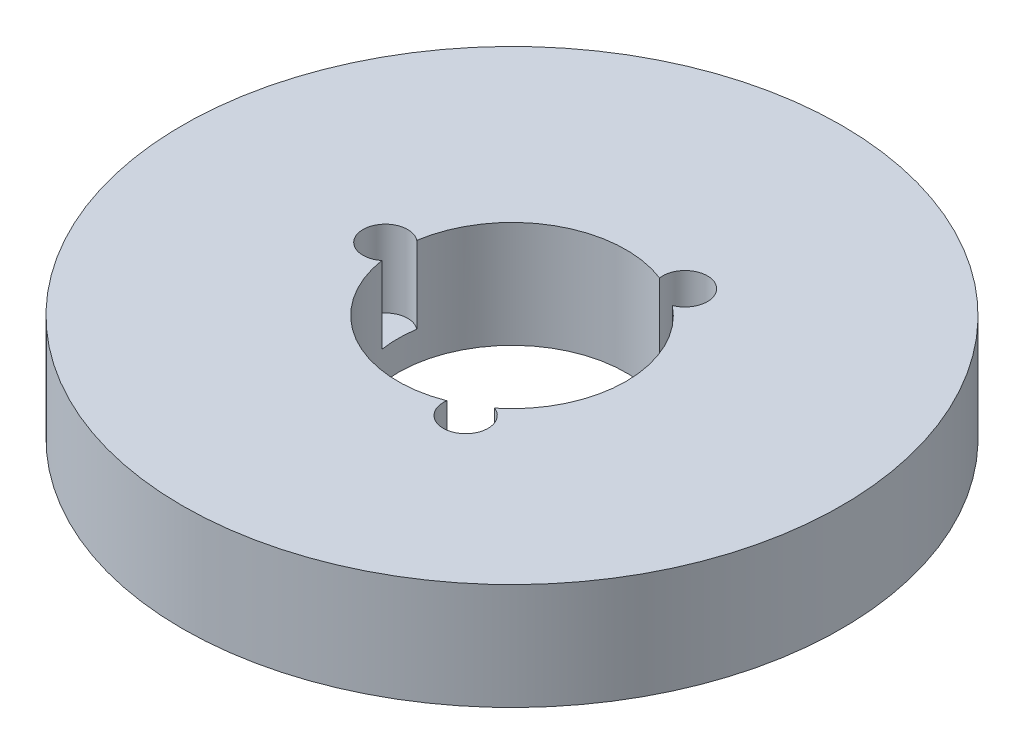
SolidWorks part; units mm, degrees
ref_plane "Front Plane" through (0, 0, 0) normal (0, 0, 1) x (1, 0, 0)
ref_plane "Top Plane" through (0, 0, 0) normal (0, 1, 0) x (1, 0, 0)
ref_plane "Right Plane" through (0, 0, 0) normal (1, 0, 0) x (0, 0, -1)
sketch "Sketch1" plane through (0, 0, 0) normal (0, 1, 0) x (1, 0, 0)
  circle A0 centre (0, 0) radius 65
  dimension "FLANGE_OD" = 130
extrude "Boss-Extrude1" add sketch "Sketch1" along normal blind 21
sketch "Sketch2" plane through (0, 0, 0) normal (0, 1, 0) x (1, 0, 0)
  circle A0 centre (0, 0) radius 22.5
  dimension "BORE_D" = 45
extrude "Cut-Extrude1" cut sketch "Sketch2" along normal through all
sketch "Sketch3" plane through (0, 21, 0) normal (0, 1, 0) x (1, 0, 0)
  circle A0 centre (0, 0) radius 24.9844 construction
  circle A1 centre (-24.9844, 0) radius 4.4141
  dimension "BOLT_D" = 8.8282
  dimension "BOLT_PCD" = 49.9688
extrude "Cut-Extrude2" cut sketch "Sketch3" against normal blind 15.1782
pattern_circular "CirPattern1" count 3 over 360 about axis through (0, 0, 0) along (0, 1, 0) of "Cut-Extrude2"
